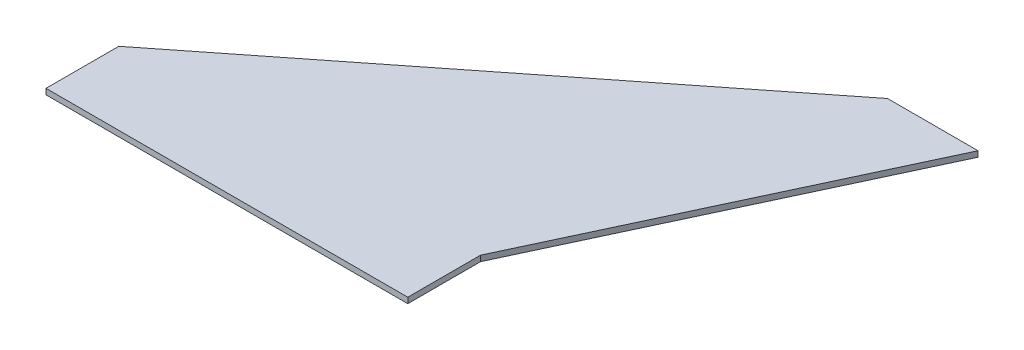
SolidWorks part; units mm, degrees
ref_plane "Front Plane" through (0, 0, 0) normal (0, 0, 1) x (1, 0, 0)
ref_plane "Top Plane" through (0, 0, 0) normal (0, 1, 0) x (1, 0, 0)
ref_plane "Right Plane" through (0, 0, 0) normal (1, 0, 0) x (0, 0, -1)
sketch "Sketch1" plane through (0, 0, 0) normal (0, 1, 0) x (1, 0, 0)
  line L0 (0, 40.894) -> (241.3, 231.394)
  line L1 (0, 0) -> (203.2, 0)
  line L2 (0, 0) -> (0, 40.894)
  line L4 (203.2, 0) -> (203.2, 40.894)
  line L6 (292.1, 231.394) -> (203.2, 40.894)
  line L7 (292.1, 231.394) -> (241.3, 231.394)
  line L8 (0, 40.894) -> (203.2, 40.894) construction
  point P5 (234.0021, 229.7108)
  dimension "D1" = 203.2
  dimension "D2" = 50.8
  dimension "D3" = 190.5
  dimension "D4" = 241.3
  dimension "D6" = 40.894
extrude "Boss-Extrude1" add sketch "Sketch1" along normal blind 3.175 contours L1 L4 L2 | L6 L0 region at (150.7564, 0, -92.3855)
